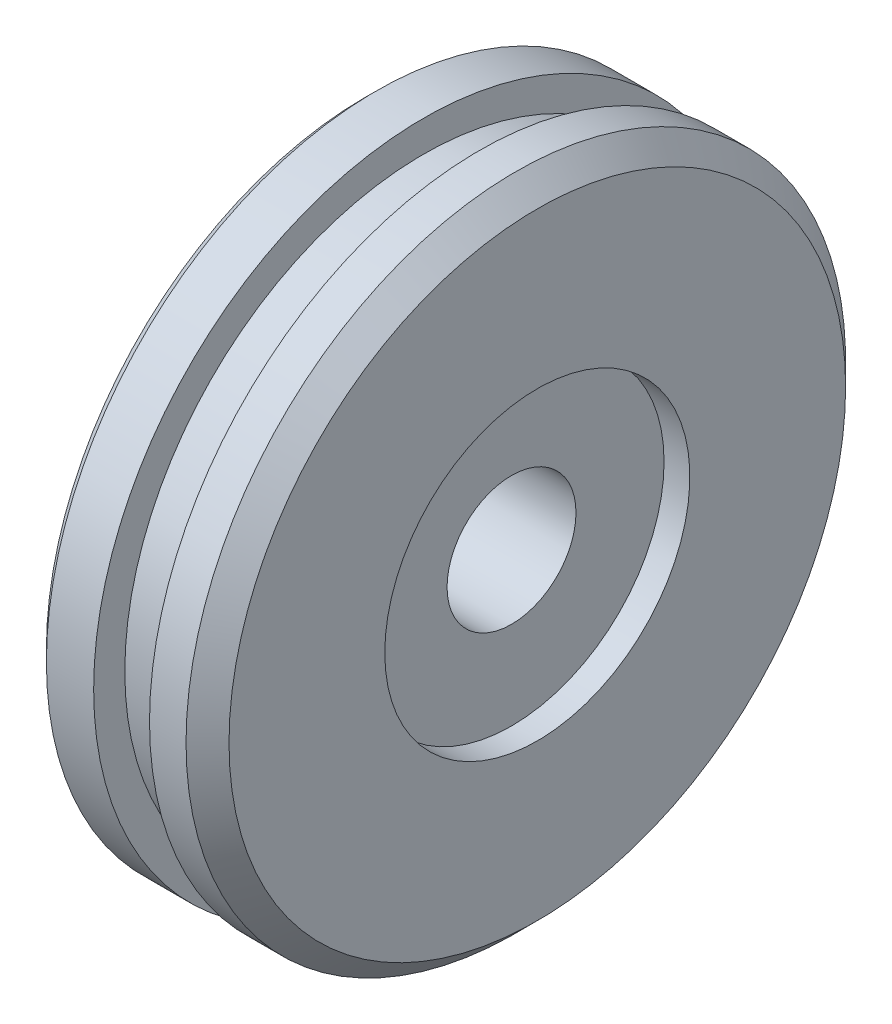
SolidWorks part; units mm, degrees
ref_plane "Front Plane" through (0, 0, 0) normal (0, 0, 1) x (1, 0, 0)
ref_plane "Top Plane" through (0, 0, 0) normal (0, 1, 0) x (1, 0, 0)
ref_plane "Right Plane" through (0, 0, 0) normal (1, 0, 0) x (0, 0, -1)
ref_plane "Plane1" through (0, 0, 66) normal (0, 0, 1) x (1, 0, 0)
sketch "Sketch1" plane through (0, 0, 66) normal (0, 0, 1) x (1, 0, 0)
  line L0 (72.2, -65) -> (90.2, -65) construction
  line L1 (77.2, -65) -> (85.2, -65)
  line L2 (85.2, -65) -> (85.2, -50.65)
  line L3 (85.2, -50.65) -> (84.2, -49.65)
  line L4 (84.2, -49.65) -> (77.7, -49.65)
  line L5 (77.7, -49.65) -> (77.2, -50.15)
  line L6 (77.2, -50.15) -> (77.2, -65)
revolve "Revolve1" add sketch "Sketch1" angle 360 about L0
sketch "Sketch2" plane through (0, 0, 66) normal (0, 0, 1) x (1, 0, 0)
  line L0 (74.9, -65) -> (87.5, -65) construction
  line L1 (79.9, -51.1) -> (82.5, -51.1)
  line L2 (82.5, -51.1) -> (82.5, -48.65)
  line L3 (82.5, -48.65) -> (79.9, -48.65)
  line L4 (79.9, -48.65) -> (79.9, -51.1)
revolve "Revolve2" add sketch "Sketch2" angle 360 about L0
combine bodies "Combine1" operation type subtract main body 101 bodies to subtract 102
sketch "Sketch3" plane through (0, 0, 0) normal (0, 0, 1) x (1, 0, 0)
  line L1 (76.7, -76.5) -> (79, -76.5)
  line L2 (76.7, -76.5) -> (76.7, -53.5)
  line L3 (76.7, -53.5) -> (79, -53.5)
  line L4 (79, -76.5) -> (79, -53.5)
extrude "Boss-Extrude1" add sketch "Sketch3" along normal blind 6.6 from offset 62.7 separate body
combine bodies "Combine2" operation type subtract main body 103 bodies to subtract 104
sketch "Sketch4" plane through (0, 0, 0) normal (0, 0, 1) x (1, 0, 0)
  line L1 (76.7, -68.3) -> (79, -68.3)
  line L2 (76.7, -68.3) -> (76.7, -61.7)
  line L3 (76.7, -61.7) -> (79, -61.7)
  line L4 (79, -68.3) -> (79, -61.7)
extrude "Boss-Extrude2" add sketch "Sketch4" along normal blind 23 from offset 54.5 separate body
combine bodies "Combine3" operation type subtract main body 105 bodies to subtract 106
sketch "Sketch5" plane through (0, 0, 0) normal (1, 0, 0) x (0, 0, -1)
  circle A0 centre (-66, -65) radius 4.6
extrude "Boss-Extrude3" add sketch "Sketch5" along normal blind 2.3 from offset 76.7 separate body
combine bodies "Combine4" operation type subtract main body 107 bodies to subtract 108
sketch "Sketch6" plane through (0, 0, 0) normal (1, 0, 0) x (0, 0, -1)
  circle A0 centre (-66, -65) radius 7.1
extrude "Boss-Extrude4" add sketch "Sketch6" along normal blind 1.7 from offset 84 separate body
combine bodies "Combine5" operation type subtract main body 109 bodies to subtract 110
sketch "Sketch7" plane through (0, 0, 0) normal (1, 0, 0) x (0, 0, -1)
  circle A0 centre (-66, -65) radius 3
extrude "Boss-Extrude5" add sketch "Sketch7" along normal blind 5.2 from offset 78.9 separate body
combine bodies "Combine6" operation type subtract main body 111 bodies to subtract 112
sketch "Sketch8" plane through (0, 0, 0) normal (0, 0, 1) x (1, 0, 0)
  line L1 (78.9, -59.5) -> (83, -59.5)
  line L2 (78.9, -59.5) -> (78.9, -57.4)
  line L3 (78.9, -57.4) -> (83, -57.4)
  line L4 (83, -59.5) -> (83, -57.4)
extrude "Boss-Extrude6" add sketch "Sketch8" along normal blind 1.8 from offset 65.1 separate body
combine bodies "Combine7" operation type subtract main body 113 bodies to subtract 114
sketch "Sketch9" plane through (0, 0, 0) normal (0, 0, 1) x (1, 0, 0)
  line L1 (78.9, -65.9) -> (83, -65.9)
  line L2 (78.9, -65.9) -> (78.9, -64.1)
  line L3 (78.9, -64.1) -> (83, -64.1)
  line L4 (83, -65.9) -> (83, -64.1)
extrude "Boss-Extrude7" add sketch "Sketch9" along normal blind 2.1 from offset 71.5 separate body
combine bodies "Combine8" operation type subtract main body 115 bodies to subtract 116
sketch "Sketch10" plane through (0, 0, 0) normal (0, 0, 1) x (1, 0, 0)
  line L1 (78.9, -72.6) -> (83, -72.6)
  line L2 (78.9, -72.6) -> (78.9, -70.5)
  line L3 (78.9, -70.5) -> (83, -70.5)
  line L4 (83, -72.6) -> (83, -70.5)
extrude "Boss-Extrude8" add sketch "Sketch10" along normal blind 1.8 from offset 65.1 separate body
combine bodies "Combine9" operation type subtract main body 117 bodies to subtract 118
sketch "Sketch11" plane through (0, 0, 0) normal (0, 0, 1) x (1, 0, 0)
  line L1 (78.9, -65.9) -> (83, -65.9)
  line L2 (78.9, -65.9) -> (78.9, -64.1)
  line L3 (78.9, -64.1) -> (83, -64.1)
  line L4 (83, -65.9) -> (83, -64.1)
extrude "Boss-Extrude9" add sketch "Sketch11" along normal blind 2.1 from offset 58.4 separate body
combine bodies "Combine10" operation type subtract main body 119 bodies to subtract 120
sketch "Sketch12" plane through (0, 0, 0) normal (0, 0, 1) x (1, 0, 0)
  line L1 (78.9, -57.4) -> (84.2, -57.4)
  line L2 (78.9, -57.4) -> (78.9, -55)
  line L3 (78.9, -55) -> (84.2, -55)
  line L4 (84.2, -57.4) -> (84.2, -55)
extrude "Boss-Extrude10" add sketch "Sketch12" along normal blind 1.8 from offset 65.1 separate body
combine bodies "Combine11" operation type subtract main body 121 bodies to subtract 122
sketch "Sketch13" plane through (0, 0, 0) normal (0, 0, 1) x (1, 0, 0)
  line L1 (78.9, -65.9) -> (84.2, -65.9)
  line L2 (78.9, -65.9) -> (78.9, -64.1)
  line L3 (78.9, -64.1) -> (84.2, -64.1)
  line L4 (84.2, -65.9) -> (84.2, -64.1)
extrude "Boss-Extrude11" add sketch "Sketch13" along normal blind 2.4 from offset 73.6 separate body
combine bodies "Combine12" operation type subtract main body 123 bodies to subtract 124
sketch "Sketch14" plane through (0, 0, 0) normal (0, 0, 1) x (1, 0, 0)
  line L1 (78.9, -75) -> (84.2, -75)
  line L2 (78.9, -75) -> (78.9, -72.6)
  line L3 (78.9, -72.6) -> (84.2, -72.6)
  line L4 (84.2, -75) -> (84.2, -72.6)
extrude "Boss-Extrude12" add sketch "Sketch14" along normal blind 1.8 from offset 65.1 separate body
combine bodies "Combine13" operation type subtract main body 125 bodies to subtract 126
sketch "Sketch15" plane through (0, 0, 0) normal (0, 0, 1) x (1, 0, 0)
  line L1 (78.9, -65.9) -> (84.2, -65.9)
  line L2 (78.9, -65.9) -> (78.9, -64.1)
  line L3 (78.9, -64.1) -> (84.2, -64.1)
  line L4 (84.2, -65.9) -> (84.2, -64.1)
extrude "Boss-Extrude13" add sketch "Sketch15" along normal blind 2.4 from offset 56 separate body
combine bodies "Combine14" operation type subtract main body 127 bodies to subtract 128
